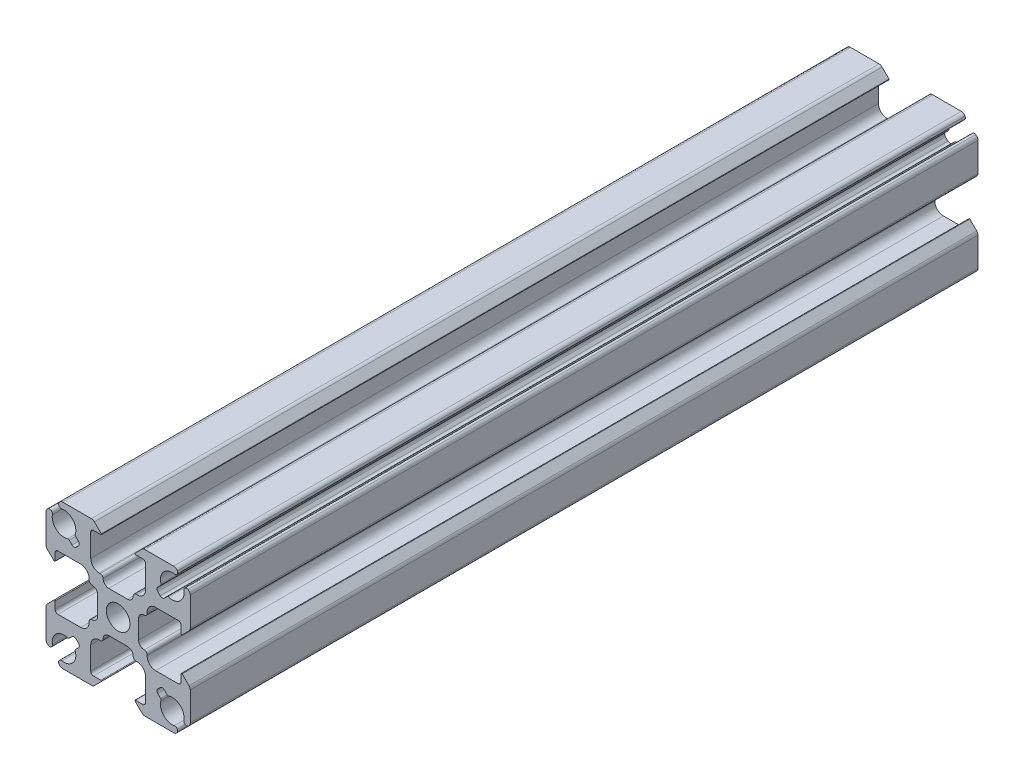
SolidWorks part; units mm, degrees
ref_plane "Front Plane" through (0, 0, 0) normal (0, 0, 1) x (1, 0, 0)
ref_plane "Top Plane" through (0, 0, 0) normal (0, 1, 0) x (1, 0, 0)
ref_plane "Right Plane" through (0, 0, 0) normal (1, 0, 0) x (0, 0, -1)
ref_plane "Plane1" through (0, 0, 0) normal (0, 0, -1) x (-1, 0, 0)
sketch "Sketch1" plane through (0, 0, 0) normal (0, 0, -1) x (-1, 0, 0)
  line L0 (-7.4885, 8.6199) -> (-6.9856, 8.117)
  line L1 (-6.9856, 7.4099) -> (-7.4099, 6.9856)
  line L2 (-8.117, 6.9856) -> (-8.6199, 7.4885)
  line L3 (-12.7, 9.7594) -> (-12.7, 4.7107)
  line L4 (-12.4803, 4.1803) -> (-11.2707, 2.9707)
  line L5 (-11.1, 3.0414) -> (-11.1, 4.325)
  line L6 (-10.6, 4.825) -> (-6.6, 4.825)
  line L7 (-5.1, 3.325) -> (-5.1, 3.15)
  line L8 (-3.6, 1.65) -> (-3.6, -1.65)
  line L9 (-5.1, -3.15) -> (-5.1, -3.325)
  line L10 (-6.6, -4.825) -> (-10.6, -4.825)
  line L11 (-11.1, -4.325) -> (-11.1, -3.0414)
  line L12 (-11.2707, -2.9707) -> (-12.4803, -4.1803)
  line L13 (-12.7, -4.7107) -> (-12.7, -9.7594)
  line L14 (-8.6199, -7.4885) -> (-8.117, -6.9856)
  line L15 (-7.4099, -6.9856) -> (-6.9856, -7.4099)
  line L16 (-6.9856, -8.117) -> (-7.4885, -8.6199)
  line L17 (-9.7594, -12.7) -> (-4.7107, -12.7)
  line L18 (-4.1803, -12.4803) -> (-2.9707, -11.2707)
  line L19 (-3.0414, -11.1) -> (-4.325, -11.1)
  line L20 (-4.825, -10.6) -> (-4.825, -6.6)
  line L21 (-3.325, -5.1) -> (-3.15, -5.1)
  line L22 (-1.65, -3.6) -> (1.65, -3.6)
  line L23 (3.15, -5.1) -> (3.325, -5.1)
  line L24 (4.825, -6.6) -> (4.825, -10.6)
  line L25 (4.325, -11.1) -> (3.0414, -11.1)
  line L26 (2.9707, -11.2707) -> (4.1803, -12.4803)
  line L27 (4.7107, -12.7) -> (9.7594, -12.7)
  line L28 (7.4885, -8.6199) -> (6.9856, -8.117)
  line L29 (6.9856, -7.4099) -> (7.4099, -6.9856)
  line L30 (8.117, -6.9856) -> (8.6199, -7.4885)
  line L31 (12.7, -9.7594) -> (12.7, -4.7107)
  line L32 (12.4803, -4.1803) -> (11.2707, -2.9707)
  line L33 (11.1, -3.0414) -> (11.1, -4.325)
  line L34 (10.6, -4.825) -> (6.6, -4.825)
  line L35 (5.1, -3.325) -> (5.1, -3.15)
  line L36 (3.6, -1.65) -> (3.6, 1.65)
  line L37 (5.1, 3.15) -> (5.1, 3.325)
  line L38 (6.6, 4.825) -> (10.6, 4.825)
  line L39 (11.1, 4.325) -> (11.1, 3.0414)
  line L40 (11.2707, 2.9707) -> (12.4803, 4.1803)
  line L41 (12.7, 4.7107) -> (12.7, 9.7594)
  line L42 (8.6199, 7.4885) -> (8.117, 6.9856)
  line L43 (7.4099, 6.9856) -> (6.9856, 7.4099)
  line L44 (6.9856, 8.117) -> (7.4885, 8.6199)
  line L45 (9.7594, 12.7) -> (4.7107, 12.7)
  line L46 (4.1803, 12.4803) -> (2.9707, 11.2707)
  line L47 (3.0414, 11.1) -> (4.325, 11.1)
  line L48 (4.825, 10.6) -> (4.825, 6.6)
  line L49 (3.325, 5.1) -> (3.15, 5.1)
  line L50 (1.65, 3.6) -> (-1.65, 3.6)
  line L51 (-3.15, 5.1) -> (-3.325, 5.1)
  line L52 (-4.825, 6.6) -> (-4.825, 10.6)
  line L53 (-4.325, 11.1) -> (-3.0414, 11.1)
  line L54 (-2.9707, 11.2707) -> (-4.1803, 12.4803)
  line L55 (-4.7107, 12.7) -> (-9.7594, 12.7)
  circle A0 centre (0, 0) radius 2.08
  arc A1 (-9.7594, 12.7) -> (-10.4266, 12.2927) centre (-9.7594, 11.95) ccw
  arc A2 (-10.4266, 12.2927) -> (-9.8933, 11.5721) centre (-9.9818, 12.0642) ccw
  arc A3 (-9.8933, 11.5721) -> (-7.5492, 8.8748) centre (-9.525, 9.525) cw
  arc A4 (-7.5492, 8.8748) -> (-7.4885, 8.6199) centre (-7.3118, 8.7967) ccw
  arc A5 (-6.9856, 8.117) -> (-6.9856, 7.4099) centre (-7.3392, 7.7635) cw
  arc A6 (-7.4099, 6.9856) -> (-8.117, 6.9856) centre (-7.7635, 7.3392) cw
  arc A7 (-8.6199, 7.4885) -> (-8.8748, 7.5492) centre (-8.7967, 7.3118) ccw
  arc A8 (-8.8748, 7.5492) -> (-11.5721, 9.8933) centre (-9.525, 9.525) cw
  arc A9 (-11.5721, 9.8933) -> (-12.2927, 10.4266) centre (-12.0642, 9.9818) ccw
  arc A10 (-12.2927, 10.4266) -> (-12.7, 9.7594) centre (-11.95, 9.7594) ccw
  arc A11 (-12.7, 4.7107) -> (-12.4803, 4.1803) centre (-11.95, 4.7107) ccw
  arc A12 (-11.2707, 2.9707) -> (-11.1, 3.0414) centre (-11.2, 3.0414) ccw
  arc A13 (-11.1, 4.325) -> (-10.6, 4.825) centre (-10.6, 4.325) cw
  arc A14 (-6.6, 4.825) -> (-5.1, 3.325) centre (-6.6, 3.325) cw
  arc A15 (-5.1, 3.15) -> (-4.6, 2.65) centre (-4.6, 3.15) ccw
  arc A16 (-4.6, 2.65) -> (-3.6, 1.65) centre (-4.6, 1.65) cw
  arc A17 (-3.6, -1.65) -> (-4.6, -2.65) centre (-4.6, -1.65) cw
  arc A18 (-4.6, -2.65) -> (-5.1, -3.15) centre (-4.6, -3.15) ccw
  arc A19 (-5.1, -3.325) -> (-6.6, -4.825) centre (-6.6, -3.325) cw
  arc A20 (-10.6, -4.825) -> (-11.1, -4.325) centre (-10.6, -4.325) cw
  arc A21 (-11.1, -3.0414) -> (-11.2707, -2.9707) centre (-11.2, -3.0414) ccw
  arc A22 (-12.4803, -4.1803) -> (-12.7, -4.7107) centre (-11.95, -4.7107) ccw
  arc A23 (-12.7, -9.7594) -> (-12.2927, -10.4266) centre (-11.95, -9.7594) ccw
  arc A24 (-12.2927, -10.4266) -> (-11.5721, -9.8933) centre (-12.0642, -9.9818) ccw
  arc A25 (-11.5721, -9.8933) -> (-8.8748, -7.5492) centre (-9.525, -9.525) cw
  arc A26 (-8.8748, -7.5492) -> (-8.6199, -7.4885) centre (-8.7967, -7.3118) ccw
  arc A27 (-8.117, -6.9856) -> (-7.4099, -6.9856) centre (-7.7635, -7.3392) cw
  arc A28 (-6.9856, -7.4099) -> (-6.9856, -8.117) centre (-7.3392, -7.7635) cw
  arc A29 (-7.4885, -8.6199) -> (-7.5492, -8.8748) centre (-7.3118, -8.7967) ccw
  arc A30 (-7.5492, -8.8748) -> (-9.8933, -11.5721) centre (-9.525, -9.525) cw
  arc A31 (-9.8933, -11.5721) -> (-10.4266, -12.2927) centre (-9.9818, -12.0642) ccw
  arc A32 (-10.4266, -12.2927) -> (-9.7594, -12.7) centre (-9.7594, -11.95) ccw
  arc A33 (-4.7107, -12.7) -> (-4.1803, -12.4803) centre (-4.7107, -11.95) ccw
  arc A34 (-2.9707, -11.2707) -> (-3.0414, -11.1) centre (-3.0414, -11.2) ccw
  arc A35 (-4.325, -11.1) -> (-4.825, -10.6) centre (-4.325, -10.6) cw
  arc A36 (-4.825, -6.6) -> (-3.325, -5.1) centre (-3.325, -6.6) cw
  arc A37 (-3.15, -5.1) -> (-2.65, -4.6) centre (-3.15, -4.6) ccw
  arc A38 (-2.65, -4.6) -> (-1.65, -3.6) centre (-1.65, -4.6) cw
  arc A39 (1.65, -3.6) -> (2.65, -4.6) centre (1.65, -4.6) cw
  arc A40 (2.65, -4.6) -> (3.15, -5.1) centre (3.15, -4.6) ccw
  arc A41 (3.325, -5.1) -> (4.825, -6.6) centre (3.325, -6.6) cw
  arc A42 (4.825, -10.6) -> (4.325, -11.1) centre (4.325, -10.6) cw
  arc A43 (3.0414, -11.1) -> (2.9707, -11.2707) centre (3.0414, -11.2) ccw
  arc A44 (4.1803, -12.4803) -> (4.7107, -12.7) centre (4.7107, -11.95) ccw
  arc A45 (9.7594, -12.7) -> (10.4266, -12.2927) centre (9.7594, -11.95) ccw
  arc A46 (10.4266, -12.2927) -> (9.8933, -11.5721) centre (9.9818, -12.0642) ccw
  arc A47 (9.8933, -11.5721) -> (7.5492, -8.8748) centre (9.525, -9.525) cw
  arc A48 (7.5492, -8.8748) -> (7.4885, -8.6199) centre (7.3118, -8.7967) ccw
  arc A49 (6.9856, -8.117) -> (6.9856, -7.4099) centre (7.3392, -7.7635) cw
  arc A50 (7.4099, -6.9856) -> (8.117, -6.9856) centre (7.7635, -7.3392) cw
  arc A51 (8.6199, -7.4885) -> (8.8748, -7.5492) centre (8.7967, -7.3118) ccw
  arc A52 (8.8748, -7.5492) -> (11.5721, -9.8933) centre (9.525, -9.525) cw
  arc A53 (11.5721, -9.8933) -> (12.2927, -10.4266) centre (12.0642, -9.9818) ccw
  arc A54 (12.2927, -10.4266) -> (12.7, -9.7594) centre (11.95, -9.7594) ccw
  arc A55 (12.7, -4.7107) -> (12.4803, -4.1803) centre (11.95, -4.7107) ccw
  arc A56 (11.2707, -2.9707) -> (11.1, -3.0414) centre (11.2, -3.0414) ccw
  arc A57 (11.1, -4.325) -> (10.6, -4.825) centre (10.6, -4.325) cw
  arc A58 (6.6, -4.825) -> (5.1, -3.325) centre (6.6, -3.325) cw
  arc A59 (5.1, -3.15) -> (4.6, -2.65) centre (4.6, -3.15) ccw
  arc A60 (4.6, -2.65) -> (3.6, -1.65) centre (4.6, -1.65) cw
  arc A61 (3.6, 1.65) -> (4.6, 2.65) centre (4.6, 1.65) cw
  arc A62 (4.6, 2.65) -> (5.1, 3.15) centre (4.6, 3.15) ccw
  arc A63 (5.1, 3.325) -> (6.6, 4.825) centre (6.6, 3.325) cw
  arc A64 (10.6, 4.825) -> (11.1, 4.325) centre (10.6, 4.325) cw
  arc A65 (11.1, 3.0414) -> (11.2707, 2.9707) centre (11.2, 3.0414) ccw
  arc A66 (12.4803, 4.1803) -> (12.7, 4.7107) centre (11.95, 4.7107) ccw
  arc A67 (12.7, 9.7594) -> (12.2927, 10.4266) centre (11.95, 9.7594) ccw
  arc A68 (12.2927, 10.4266) -> (11.5721, 9.8933) centre (12.0642, 9.9818) ccw
  arc A69 (11.5721, 9.8933) -> (8.8748, 7.5492) centre (9.525, 9.525) cw
  arc A70 (8.8748, 7.5492) -> (8.6199, 7.4885) centre (8.7967, 7.3118) ccw
  arc A71 (8.117, 6.9856) -> (7.4099, 6.9856) centre (7.7635, 7.3392) cw
  arc A72 (6.9856, 7.4099) -> (6.9856, 8.117) centre (7.3392, 7.7635) cw
  arc A73 (7.4885, 8.6199) -> (7.5492, 8.8748) centre (7.3118, 8.7967) ccw
  arc A74 (7.5492, 8.8748) -> (9.8933, 11.5721) centre (9.525, 9.525) cw
  arc A75 (9.8933, 11.5721) -> (10.4266, 12.2927) centre (9.9818, 12.0642) ccw
  arc A76 (10.4266, 12.2927) -> (9.7594, 12.7) centre (9.7594, 11.95) ccw
  arc A77 (4.7107, 12.7) -> (4.1803, 12.4803) centre (4.7107, 11.95) ccw
  arc A78 (2.9707, 11.2707) -> (3.0414, 11.1) centre (3.0414, 11.2) ccw
  arc A79 (4.325, 11.1) -> (4.825, 10.6) centre (4.325, 10.6) cw
  arc A80 (4.825, 6.6) -> (3.325, 5.1) centre (3.325, 6.6) cw
  arc A81 (3.15, 5.1) -> (2.65, 4.6) centre (3.15, 4.6) ccw
  arc A82 (2.65, 4.6) -> (1.65, 3.6) centre (1.65, 4.6) cw
  arc A83 (-1.65, 3.6) -> (-2.65, 4.6) centre (-1.65, 4.6) cw
  arc A84 (-2.65, 4.6) -> (-3.15, 5.1) centre (-3.15, 4.6) ccw
  arc A85 (-3.325, 5.1) -> (-4.825, 6.6) centre (-3.325, 6.6) cw
  arc A86 (-4.825, 10.6) -> (-4.325, 11.1) centre (-4.325, 10.6) cw
  arc A87 (-3.0414, 11.1) -> (-2.9707, 11.2707) centre (-3.0414, 11.2) ccw
  arc A88 (-4.1803, 12.4803) -> (-4.7107, 12.7) centre (-4.7107, 11.95) ccw
extrude "Boss-Extrude1" add sketch "Sketch1" against normal mid plane 138.683
hole_wizard "Tap Drill for M6x1.0 Tap1" positions "Sketch3" profile "Sketch2" hole size "M6x1.0" standard "ANSI Metric" end condition through all
sketch "Sketch3" plane through (0, 3.6, 0) normal (0, 1, 0) x (1, 0, 0)
  line L0 (-1.65, -69.3415) -> (1.65, -69.3415) construction
  point P0 (0, -56.6415)
  point P2 (0, -5.8415)
  point P5 (0, -69.3415)
  point P14 (0, -69.3415)
  dimension "D1" = 12.7
  dimension "D2" = 63.5
sketch "Sketch2" plane through (0, 3.6, 56.6415) normal (1, 0, 0) x (0, 0, 1)
  line L0 (0, 0) -> (0, 16.3)
  line L1 (0, 16.3) -> (2.5, 16.3)
  line L2 (2.5, 16.3) -> (2.5, 0)
  line L5 (2.5, 0) -> (0, 0)
  line L11 (0, -6.35) -> (0, 107.95) construction
  dimension "Thru Hole Dia." = 5
  dimension "Thru Hole Depth" = 16.3
